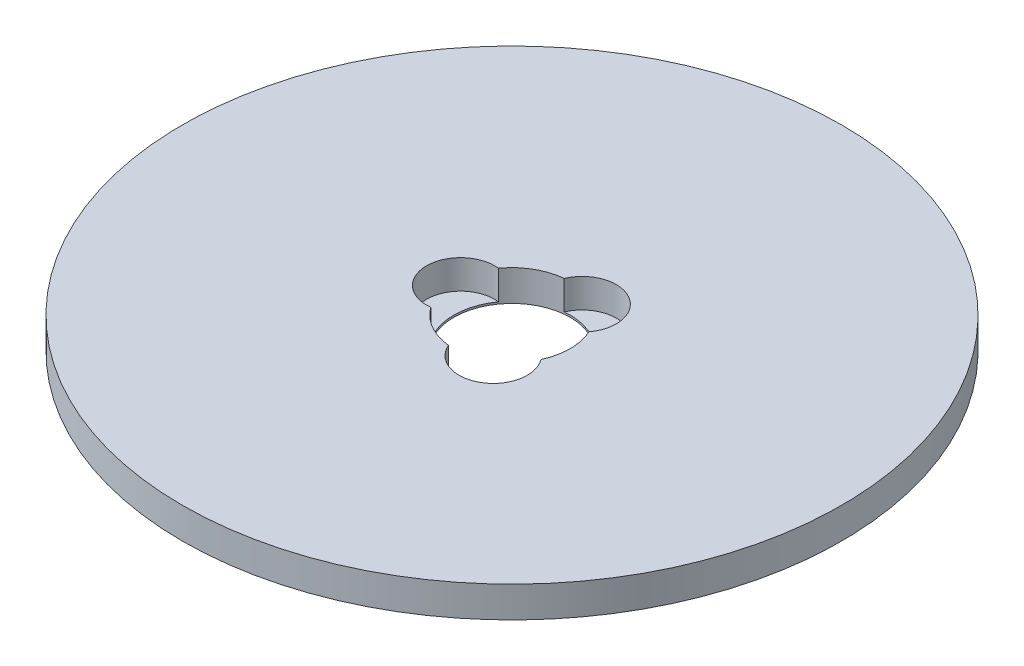
SolidWorks part; units mm, degrees
ref_plane "Front Plane" through (0, 0, 0) normal (0, 0, 1) x (1, 0, 0)
ref_plane "Top Plane" through (0, 0, 0) normal (0, 1, 0) x (1, 0, 0)
ref_plane "Right Plane" through (0, 0, 0) normal (1, 0, 0) x (0, 0, -1)
sketch "Sketch1" plane through (0, 0, 0) normal (0, 1, 0) x (1, 0, 0)
  circle A0 centre (0, 0) radius 85
  dimension "FLANGE_OD" = 170
extrude "Boss-Extrude1" add sketch "Sketch1" along normal blind 8
sketch "Sketch2" plane through (0, 0, 0) normal (0, 1, 0) x (1, 0, 0)
  circle A0 centre (0, 0) radius 15
  dimension "BORE_D" = 30
extrude "Cut-Extrude1" cut sketch "Sketch2" along normal through all
sketch "Sketch3" plane through (0, 8, 0) normal (0, 1, 0) x (1, 0, 0)
  circle A0 centre (0, 0) radius 13.2548 construction
  circle A1 centre (-13.2548, 0) radius 8.789
  dimension "BOLT_D" = 17.578
  dimension "BOLT_PCD" = 26.5096
extrude "Cut-Extrude2" cut sketch "Sketch3" against normal blind 7.4925
pattern_circular "CirPattern1" count 3 over 360 about axis through (0, 0, 0) along (0, 1, 0) of "Cut-Extrude2"
